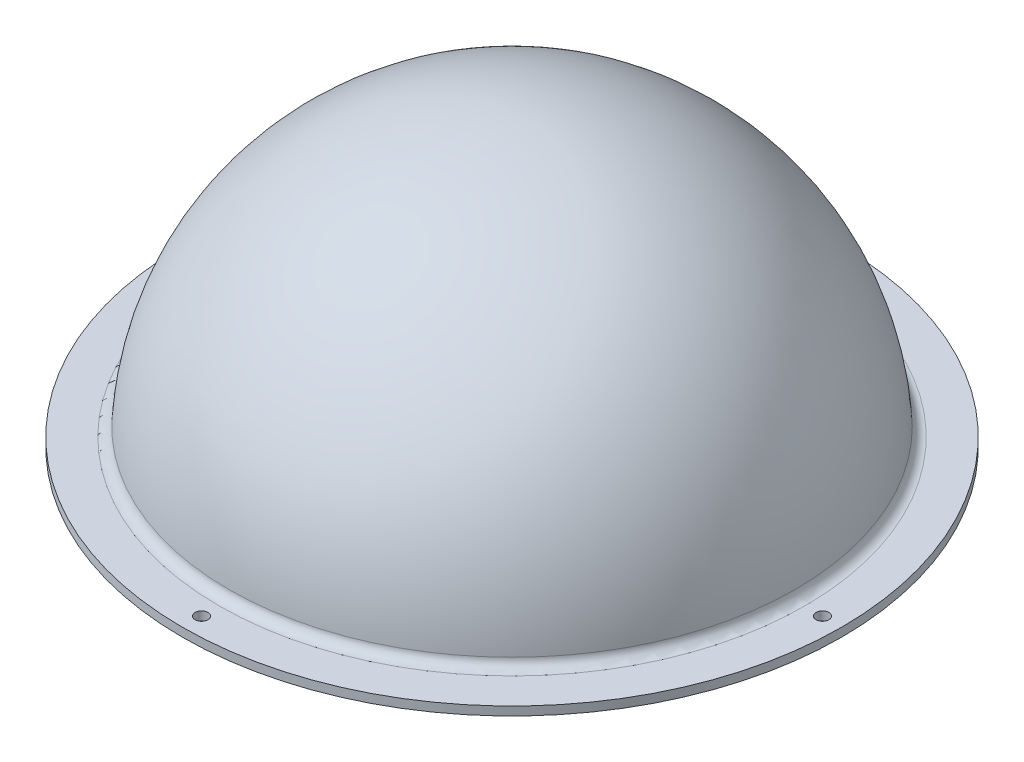
SolidWorks part; units mm, degrees
material "Acrylic (Medium-high impact)"
ref_plane "Front Plane" through (0, 0, 0) normal (0, 0, 1) x (1, 0, 0)
ref_plane "Top Plane" through (0, 0, 0) normal (0, 1, 0) x (1, 0, 0)
ref_plane "Right Plane" through (0, 0, 0) normal (1, 0, 0) x (0, 0, -1)
sketch "Sketch1" plane through (0, 0, 0) normal (0, 0, 1) x (1, 0, 0)
  line L0 (0, 0) -> (0, 73.025)
  line L1 (0, 0) -> (84.9312, 0)
  line L2 (84.9312, 0) -> (84.9312, 2.2352)
  line L3 (84.9312, 2.2352) -> (73.025, 2.2352)
  arc A0 (0, 73.025) -> (73.025, 2.2352) centre (0, -0.0353) cw
  dimension "D1" = 73.025
  dimension "D2" = 11.9062
  dimension "D3" = 2.2352
  dimension "D4" = 73.025
revolve "Revolve1" add sketch "Sketch1" angle 360 about L0
shell "Shell1" thickness 2.2352 removed face at (0, 0, -84.9312)
sketch "Sketch2" plane through (0, 2.2352, 0) normal (0, 1, 0) x (1, 0, 0)
  line L0 (0, 0) -> (0, 84.9312) construction
  circle A1 centre (0, 0) radius 84.9312 construction
  circle A2 centre (0, 0) radius 81.6292
  circle A3 centre (0, 0) radius 81.6292 construction
  circle A4 centre (0, 79.9782) radius 1.651
  circle A5 centre (0, 0) radius 79.9782 construction
  circle A6 centre (79.9782, 0) radius 1.651
  circle A7 centre (0, -79.9782) radius 1.651
  circle A8 centre (-79.9782, 0) radius 1.651
  point P19 (0, 0)
  dimension "D2" = 3.302
  dimension "D1" = 3.302
  dimension "D3" = 4
extrude "Dome Holes" cut sketch "Sketch2" against normal up to surface (2.2352 mm away) up to face at (0, 0, 70.8251)
fillet "Fillet1" radius 2.0955 1 edges at (0, 0, 70.8251)
fillet "Fillet2" radius 2.54 1 edges at (0, 2.2352, -73.025)
